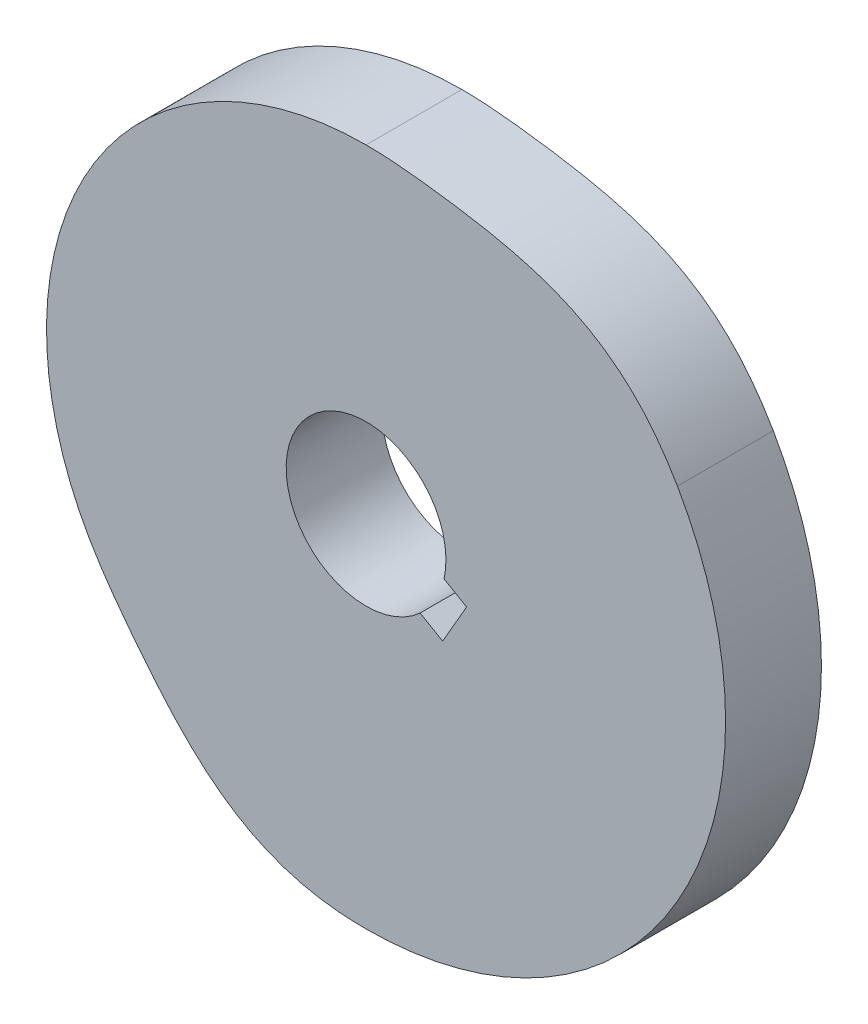
SolidWorks part; units mm, degrees
material "45"
ref_plane "前视基准面" through (0, 0, 0) normal (0, 0, 1) x (1, 0, 0)
ref_plane "上视基准面" through (0, 0, 0) normal (0, 1, 0) x (1, 0, 0)
ref_plane "右视基准面" through (0, 0, 0) normal (1, 0, 0) x (0, 0, -1)
ref_axis "基准轴1" through (0, 0, -88.99) along (0, 0, 1)
sketch "草图1" plane through (0, 0, 0) normal (0, 0, 1) x (1, 0, 0)
  arc A0 (38.9711, 22.5) -> (0, -45) centre (0, 0) cw
  arc A1 (-34.641, -20) -> (0, 40) centre (0, 0) cw
  spline S0 degree 3 poles (0, 40) (0.4654, 40) (1.1636, 39.9878) (2.0938, 39.9508) (2.7911, 39.9136) (3.488, 39.8678) (4.1847, 39.8141) (4.8813, 39.7534) (5.5777, 39.6862) (6.2744, 39.6133) (6.9714, 39.535) (7.6691, 39.452) (8.3677, 39.3644) (9.0674, 39.2725) (9.7685, 39.1765) (10.4712, 39.0763) (11.1759, 38.9719) (11.8826, 38.8631) (12.5915, 38.7497) (13.3028, 38.6311) (14.0164, 38.507) (14.7325, 38.3767) (15.4509, 38.2398) (16.1715, 38.0953) (16.8942, 37.9427) (17.6185, 37.7811) (18.3443, 37.6096) (19.071, 37.4274) (19.7982, 37.2337) (20.5253, 37.0275) (21.2516, 36.808) (21.9765, 36.5744) (22.6992, 36.3259) (23.4189, 36.0617) (24.1348, 35.7812) (24.846, 35.4838) (25.5515, 35.1688) (26.2505, 34.8359) (26.9421, 34.4846) (27.6253, 34.1148) (28.2992, 33.7261) (28.963, 33.3186) (29.6159, 32.8922) (30.257, 32.447) (30.8856, 31.9833) (31.5011, 31.5014) (32.1029, 31.0017) (32.6905, 30.4846) (33.2634, 29.9507) (33.8214, 29.4007) (34.3642, 28.8351) (34.8917, 28.2548) (35.4038, 27.6605) (35.9006, 27.053) (36.3822, 26.4332) (36.8489, 25.8019) (37.3011, 25.1599) (37.739, 24.508) (38.3048, 23.6268) (38.7094, 22.9534) (38.9711, 22.5) knots 0 0 0 0 0.031081 0.046623 0.062166 0.077714 0.093267 0.108829 0.124403 0.139994 0.155606 0.171244 0.186914 0.202621 0.218372 0.234172 0.250026 0.265941 0.281921 0.297971 0.314095 0.330296 0.346575 0.362935 0.379376 0.395897 0.412497 0.429175 0.445928 0.462751 0.479642 0.496597 0.513609 0.530676 0.547791 0.564951 0.58215 0.599385 0.616651 0.633944 0.65126 0.668598 0.685954 0.703326 0.720713 0.738112 0.755523 0.772944 0.790375 0.807815 0.825262 0.842717 0.860179 0.877645 0.895117 0.912593 0.930071 0.947552 0.965034 1 1 1 1
  spline S1 degree 3 poles (0, -45) (-0.5236, -45) (-1.309, -44.9863) (-2.355, -44.937) (-3.1386, -44.8836) (-3.9206, -44.8131) (-4.7007, -44.7245) (-5.4783, -44.6173) (-6.2528, -44.4908) (-7.0235, -44.3445) (-7.7898, -44.1778) (-8.551, -43.9905) (-9.3064, -43.7823) (-10.0552, -43.5531) (-10.7968, -43.3028) (-11.5305, -43.0315) (-12.2556, -42.7394) (-12.9715, -42.4268) (-13.6775, -42.0942) (-14.3732, -41.742) (-15.058, -41.3709) (-15.7316, -40.9816) (-16.3935, -40.5748) (-17.0435, -40.1516) (-17.6813, -39.7127) (-18.3069, -39.2591) (-18.9201, -38.792) (-19.5209, -38.3122) (-20.1096, -37.821) (-20.6861, -37.3194) (-21.2509, -36.8084) (-21.8041, -36.2891) (-22.3462, -35.7626) (-22.8776, -35.2297) (-23.3987, -34.6914) (-23.9101, -34.1486) (-24.4123, -33.6021) (-24.9058, -33.0526) (-25.3912, -32.5008) (-25.869, -31.9471) (-26.3398, -31.3921) (-26.8041, -30.8361) (-27.2624, -30.2794) (-27.7152, -29.7222) (-28.1627, -29.1645) (-28.6055, -28.6065) (-29.0436, -28.048) (-29.4773, -27.4888) (-29.9067, -26.9288) (-30.3318, -26.3676) (-30.7526, -25.805) (-31.1689, -25.2404) (-31.5804, -24.6736) (-31.9868, -24.104) (-32.3877, -23.5311) (-32.7825, -22.9546) (-33.1707, -22.374) (-33.5516, -21.7887) (-34.0487, -21.0016) (-34.4083, -20.4031) (-34.641, -20) knots 0 0 0 0 0.034966 0.052448 0.069929 0.087407 0.104883 0.122355 0.139821 0.157283 0.174738 0.192185 0.209625 0.227056 0.244477 0.261888 0.279287 0.296674 0.314046 0.331402 0.34874 0.366056 0.383349 0.400615 0.41785 0.435049 0.452209 0.469324 0.486391 0.503403 0.520358 0.537249 0.554072 0.570825 0.587503 0.604103 0.620624 0.637065 0.653425 0.669704 0.685905 0.702029 0.718079 0.734059 0.749974 0.765828 0.781628 0.797379 0.813086 0.828756 0.844394 0.860006 0.875597 0.891171 0.906733 0.922286 0.937834 0.953377 0.968919 1 1 1 1
extrude "凸台-拉伸1" add sketch "草图1" along normal blind 12
sketch "草图2" plane through (0, 0, 0) normal (0, 0, 1) x (1, 0, 0)
  line L0 (9.7614, -2.1716) -> (12.5851, -3.8019)
  line L1 (12.5851, -3.8019) -> (9.5851, -8.9981)
  line L2 (9.5851, -8.9981) -> (6.7614, -7.3678)
  arc A0 (9.7614, -2.1716) -> (6.7614, -7.3678) centre (0, 0) ccw
extrude "切除-拉伸1" cut sketch "草图2" against normal blind 12 and the other way blind 12
